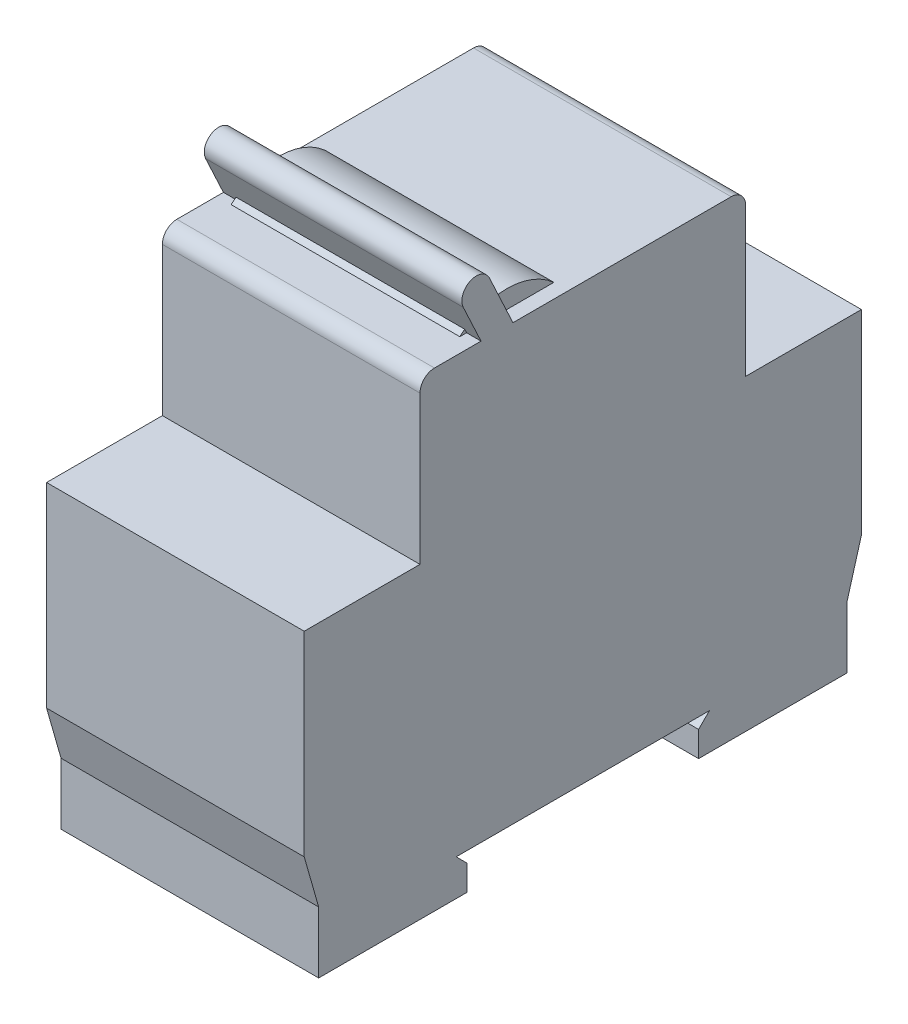
SolidWorks part; units mm, degrees
ref_plane "Спереди" through (0, 0, 0) normal (0, 0, 1) x (1, 0, 0)
ref_plane "Сверху" through (0, 0, 0) normal (0, 1, 0) x (1, 0, 0)
ref_plane "Справа" through (0, 0, 0) normal (1, 0, 0) x (0, 0, -1)
sketch "Эскиз1" plane through (0, 0, 0) normal (1, 0, 0) x (0, 0, -1)
  line L0 (-17.5001, 0) -> (17.5001, 0)
  line L1 (17.5001, 0) -> (16, -1.5)
  line L2 (16, -5) -> (36.5, -5)
  line L3 (36.5, -5) -> (36.5, 3.5)
  line L4 (36.5, 3.5) -> (38.5, 10.5)
  line L5 (38.5, 10.5) -> (38.5, 37.5)
  line L6 (38.5, 37.5) -> (22.5, 37.5)
  line L7 (22.5, 37.5) -> (22.5, 60)
  line L8 (22.5, 60) -> (-22.5, 60)
  line L9 (0, 0) -> (0, 60) construction
  line L10 (16, -1.5) -> (16, -5)
  line L11 (-16, -1.5) -> (-16, -5)
  line L12 (-22.5, 37.5) -> (-22.5, 60)
  line L13 (-38.5, 37.5) -> (-22.5, 37.5)
  line L14 (-38.5, 10.5) -> (-38.5, 37.5)
  line L15 (-36.5, 3.5) -> (-38.5, 10.5)
  line L16 (-36.5, -5) -> (-36.5, 3.5)
  line L17 (-16, -5) -> (-36.5, -5)
  line L18 (-17.5001, 0) -> (-16, -1.5)
  point P3 (0, 0)
  dimension "D1" = 45
  dimension "D2" = 77
  dimension "D3" = 73
  dimension "D4" = 18.9999
  dimension "D5" = 20.5
  dimension "D6" = 5
  dimension "D7" = 3.5
  dimension "D8" = 8.5
  dimension "D9" = 42.5
  dimension "D10" = 65
  dimension "D11" = 27
extrude "Бобышка-Вытянуть1" add sketch "Эскиз1" along normal blind 17.8 and the other way blind 17.8
sketch "Эскиз2" plane through (17.8, 0, 0) normal (1, 0, 0) x (0, 0, -1)
  line L0 (22.5, 60) -> (-22.5, 60) construction
  line L1 (-2, 60) -> (-15, 60)
  line L2 (22.5, 37.5) -> (22.5, 60) construction
  arc A0 (-2, 60) -> (-15, 60) centre (-8.5, 52.8) ccw
  dimension "D3" = 2.5
  dimension "D1" = 13
  dimension "D2" = 24.5
extrude "Бобышка-Вытянуть2" add sketch "Эскиз2" against normal offset from surface (31.6 mm away) 2 from offset 2 up to face at (-17.8, 15.2778, 0) offset against normal yes
sketch "Эскиз3" plane through (17.8, 0, 0) normal (1, 0, 0) x (0, 0, -1)
  line L0 (-14.7125, 66.1227) -> (-8.5, 52.8) construction
  line L1 (-12.8999, 66.968) -> (-6.6874, 53.6452)
  line L2 (-16.5251, 65.2775) -> (-10.3126, 51.9548)
  line L3 (22.5, 60) -> (-22.5, 60) construction
  arc A0 (-12.8999, 66.968) -> (-16.5251, 65.2775) centre (-14.7125, 66.1227) ccw
  arc A1 (-10.3126, 51.9548) -> (-6.6874, 53.6452) centre (-8.5, 52.8) ccw
  arc A2 (-2, 60) -> (-15, 60) centre (-8.5, 52.8) ccw construction
  point P2 (-11.6062, 59.4614)
  point P10 (0, 0)
  point P11 (-14.8314, 66.0666)
  dimension "D2" = 7
  dimension "D1" = 4
  dimension "D3" = 65
extrude "Бобышка-Вытянуть3" add sketch "Эскиз3" against normal up to surface (35.6 mm away) up to face at (-17.8, 15.2778, 0)
fillet "Скругление1" radius 2 2 edges at (0, 60, -22.5) (0, 60, 22.5)
